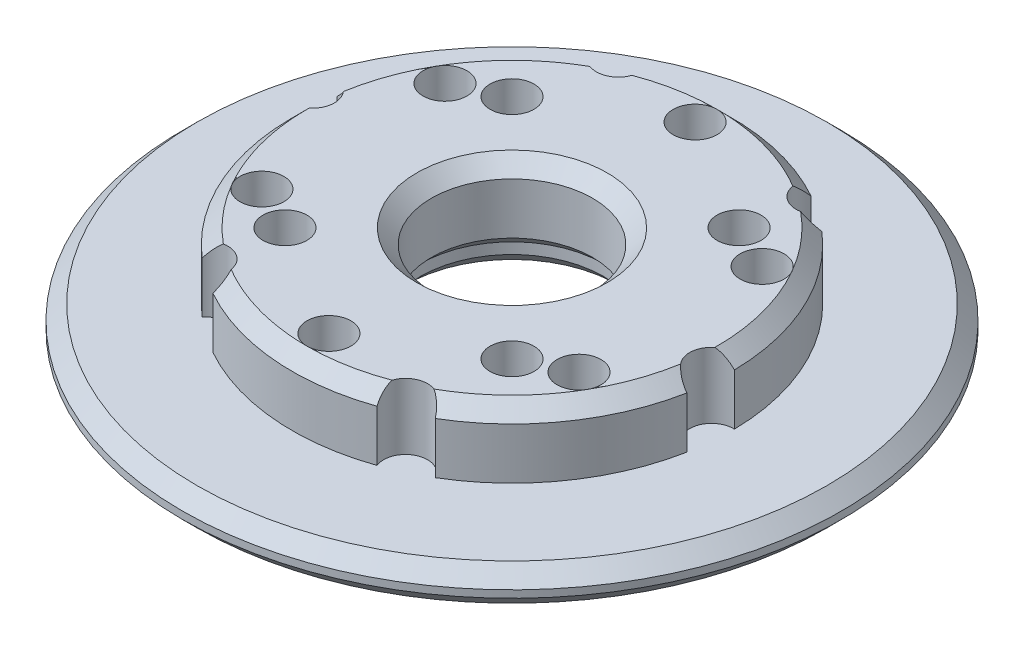
SolidWorks part; units mm, degrees
ref_plane "Front Plane" through (0, 0, 0) normal (0, 0, 1) x (1, 0, 0)
ref_plane "Top Plane" through (0, 0, 0) normal (0, 1, 0) x (1, 0, 0)
ref_plane "Right Plane" through (0, 0, 0) normal (1, 0, 0) x (0, 0, -1)
sketch "Sketch1" plane through (0, 0, 0) normal (0, 1, 0) x (1, 0, 0)
  circle A0 centre (0, 0) radius 45
  dimension "D1" = 90
extrude "Boss-Extrude1" add sketch "Sketch1" along normal blind 5
sketch "Sketch2" plane through (0, 5, 0) normal (0, 1, 0) x (1, 0, 0)
  circle A0 centre (0, 0) radius 30
  dimension "D1" = 60
extrude "Boss-Extrude2" add sketch "Sketch2" along normal blind 9
sketch "Sketch3" plane through (0, 0, 0) normal (0, -1, 0) x (1, 0, 0)
  line L1 (-15.5, 15.5) -> (15.5, 15.5)
  line L2 (-15.5, 15.5) -> (-15.5, -15.5)
  line L3 (-15.5, -15.5) -> (15.5, -15.5)
  line L4 (15.5, 15.5) -> (15.5, -15.5)
  line L5 (-15.5, 15.5) -> (15.5, -15.5) construction
  line L6 (-15.5, -15.5) -> (15.5, 15.5) construction
  circle A0 centre (-15.5, 15.5) radius 1.75
  circle A1 centre (15.5, 15.5) radius 1.75
  circle A2 centre (15.5, -15.5) radius 1.75
  circle A3 centre (-15.5, -15.5) radius 1.75
  point P0 (0, 0)
  dimension "D3" = 3.5
  dimension "D4" = 3.5
  dimension "D5" = 3.5
  dimension "D6" = 3.5
  dimension "D1" = 31
  dimension "D2" = 31
extrude "Cut-Extrude1" cut sketch "Sketch3" against normal through all contours L4 A1 L1 | L1 A1 L4 | L4 A2 L3 | L3 A2 L4 | L3 A3 L2 | L2 A3 L3 | L2 A0 L1 | L1 A0 L2 region at (-15.7476, 0, 15.7476) region at (-14.7573, 0, 14.7573) region at (15.7476, 0, 15.7476) region at (14.7573, 0, 14.7573) region at (-14.7573, 0, -14.7573) region at (-15.7476, 0, -15.7476) region at (15.7476, 0, -15.7476) region at (14.7573, 0, -14.7573)
sketch "Sketch4" plane through (0, 0, 0) normal (0, -1, 0) x (1, 0, 0)
  circle A0 centre (0, 0) radius 12.5
  dimension "D1" = 25
extrude "Cut-Extrude2" cut sketch "Sketch4" against normal blind 3
sketch "Sketch5" plane through (0, 3, 0) normal (0, -1, 0) x (1, 0, 0)
  circle A0 centre (0, 0) radius 11
  dimension "D1" = 22
extrude "Cut-Extrude3" cut sketch "Sketch5" against normal blind 18
sketch "Sketch10" plane through (0, 14, 0) normal (0, 1, 0) x (1, 0, 0)
  circle A0 centre (0, 0) radius 25 construction
  circle A1 centre (0, 25) radius 3
  circle A2 centre (21.6506, 12.5) radius 3
  circle A3 centre (21.6506, -12.5) radius 3
  circle A4 centre (0, -25) radius 3
  circle A5 centre (-21.6506, -12.5) radius 3
  circle A6 centre (-21.6506, 12.5) radius 3
  point P17 (0, 0)
  dimension "D1" = 50
  dimension "D2" = 6
  dimension "D3" = 6
extrude "Cut-Extrude4" cut sketch "Sketch10" against normal blind 7
sketch "Sketch11" plane through (0, 14, 0) normal (0, 1, 0) x (1, 0, 0)
  circle A0 centre (0, 0) radius 30 construction
  circle A1 centre (-12.6681, 27.1941) radius 3
  circle A2 centre (17.2168, 24.5679) radius 3
  circle A3 centre (29.8848, -2.6262) radius 3
  circle A4 centre (12.6681, -27.1941) radius 3
  circle A5 centre (-17.2168, -24.5679) radius 3
  circle A6 centre (-29.8848, 2.6262) radius 3
  point P17 (0, 0)
  dimension "D1" = 6
extrude "Cut-Extrude5" cut sketch "Sketch11" against normal up to surface (9 mm away) up to face at (0, 5, 30)
chamfer "Chamfer1" distance 2 angle 45 2 edges at (0, 0, 45) (0, 5, 45)
chamfer "Chamfer2" distance 2 angle 45 9 edges at (0, 0, -12.5) (0, 3, -11) (0, 14, 11) (-2.6262, 14, 29.8848) (24.5679, 14, 17.2168) (27.1941, 14, -12.6681) (2.6262, 14, -29.8848) (-24.5679, 14, -17.2168) (-27.1941, 14, 12.6681)
sketch "Sketch12" plane through (0, 14, 0) normal (0, 1, 0) x (1, 0, 0)
  circle A0 centre (-15.5, 15.5) radius 3
  circle A1 centre (15.5, 15.5) radius 3
  circle A2 centre (15.5, -15.5) radius 3
  circle A3 centre (-15.5, -15.5) radius 3
  dimension "D1" = 6
  dimension "D2" = 6
  dimension "D3" = 6
  dimension "D4" = 6
extrude "Cut-Extrude6" cut sketch "Sketch12" against normal blind 9
chamfer "Chamfer3" distance 1 angle 45 4 edges at (-15.5, 5, 17.25) (-15.5, 5, -13.75) (15.5, 5, -13.75) (15.5, 5, 17.25)
